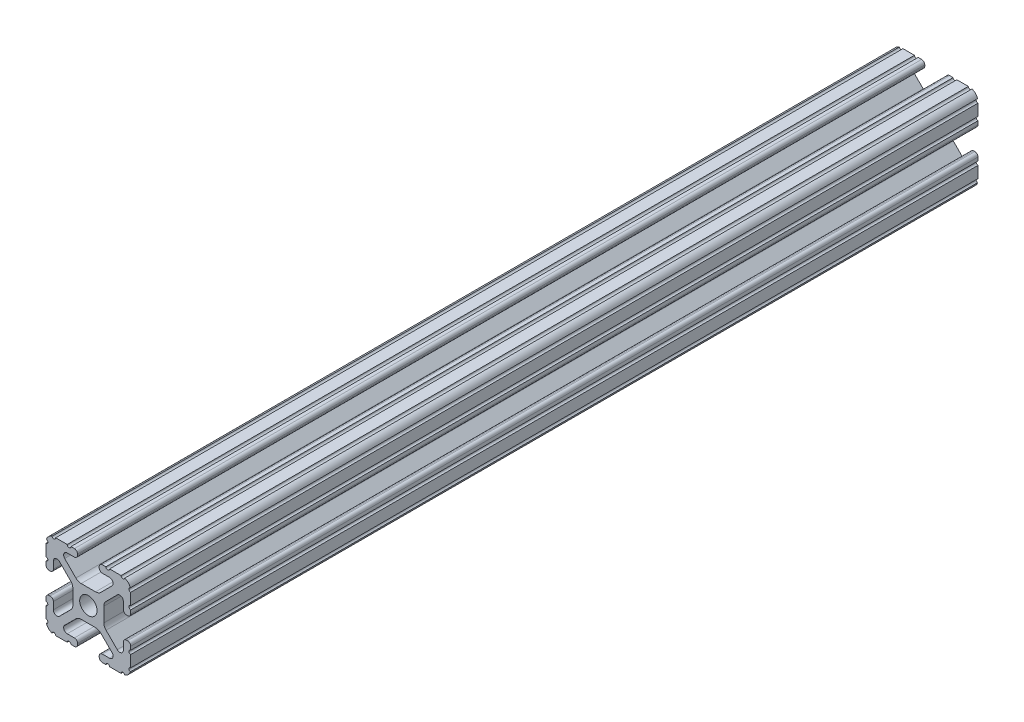
SolidWorks part; units mm, degrees
ref_plane "Front Plane" through (0, 0, 0) normal (0, 0, 1) x (1, 0, 0)
ref_plane "Top Plane" through (0, 0, 0) normal (0, 1, 0) x (1, 0, 0)
ref_plane "Right Plane" through (0, 0, 0) normal (1, 0, 0) x (0, 0, -1)
sketch "Sketch2" plane through (0, 0, 0) normal (0, 0, 1) x (1, 0, 0)
  line L0 (0, 12.7) -> (0, -12.7) construction
  line L1 (-12.7, 0) -> (12.7, 0) construction
  line L2 (3.2512, -12.7) -> (12.7, -12.7)
  line L3 (12.7, -12.7) -> (12.7, -3.2512)
  line L4 (3.2512, -12.7) -> (3.2512, -10.4902)
  line L5 (3.2512, -10.4902) -> (8.9276, -10.4902)
  line L6 (8.9276, -10.4902) -> (3.0856, -4.6482)
  line L7 (0, 0) -> (12.7, -12.7) construction
  line L8 (12.7, -3.2512) -> (10.4902, -3.2512)
  line L9 (10.4902, -3.2512) -> (10.4902, -8.9276)
  line L10 (10.4902, -8.9276) -> (4.6482, -3.0856)
  circle A0 centre (0, 0) radius 2.6035
  arc A1 (6.3485, -10.4902) -> (7.1039, -8.6665) centre (6.3485, -9.4219) ccw construction
  point P8 (0, -4.6482)
  dimension "Center Hole Diameter" = 5.207
  dimension "Rail Height" = 25.4
  dimension "Rail Width" = 25.4
  dimension "T-Slot Width" = 6.5024
  dimension "Slot Inner Width" = 14.8336
  dimension "Thickness" = 2.2098
  dimension "Slot Depth" = 5.842
  dimension "D1" = 2.2098
sketch "Sketch3" plane through (0, 0, 0) normal (1, 0, 0) x (0, 0, -1)
  line L0 (-152.4, -12.7) -> (152.4, -12.7) construction
  line L1 (-127, 0) -> (127, 0) construction
  dimension "Length" = 304.8
  dimension "D1" = 25.4
sketch "Sketch4" plane through (0, 0, 0) normal (0, 0, 1) x (1, 0, 0)
  line L0 (4.1904, -12.7) -> (10.1173, -12.7)
  line L1 (3.2512, -12.7) -> (12.7, -12.7) construction
  line L2 (3.2512, -12.7) -> (3.2512, -10.4902) construction
  line L3 (3.2512, -10.4902) -> (8.9276, -10.4902) construction
  line L4 (3.2512, -11.4294) -> (3.2512, -11.7608)
  line L5 (4.1904, -10.4902) -> (6.3485, -10.4902)
  line L6 (0, -4.6482) -> (2.164, -4.6482)
  line L7 (8.9276, -10.4902) -> (3.0856, -4.6482) construction
  line L8 (3.7373, -5.2999) -> (7.1039, -8.6665)
  line L9 (12.7, -12.7) -> (12.7, -3.2512) construction
  line L10 (10.4902, -8.9276) -> (4.6482, -3.0856) construction
  line L11 (10.4902, -3.2512) -> (10.4902, -8.9276) construction
  line L12 (10.4902, -6.3485) -> (10.4902, -4.1904)
  line L13 (12.7, -3.2512) -> (10.4902, -3.2512) construction
  line L14 (11.4294, -3.2512) -> (11.7608, -3.2512)
  line L15 (12.7, -4.1904) -> (12.7, -10.1173)
  line L16 (8.6665, -7.1039) -> (5.2999, -3.7373)
  line L17 (4.6482, 0) -> (4.6482, -2.164)
  line L18 (-12.7, 0) -> (12.7, 0) construction
  line L19 (0, -4.6482) -> (0, -2.6035)
  line L20 (0, 12.7) -> (0, -12.7) construction
  line L21 (4.6482, 0) -> (2.6035, 0)
  arc A0 (3.2512, -11.7608) -> (4.1904, -12.7) centre (4.1904, -11.7608) ccw
  arc A2 (3.2512, -11.4294) -> (4.1904, -10.4902) centre (4.1904, -11.4294) cw
  arc A3 (6.3485, -10.4902) -> (7.1039, -8.6665) centre (6.3485, -9.4219) ccw
  arc A4 (2.164, -4.6482) -> (3.7373, -5.2999) centre (2.164, -6.8732) cw
  arc A5 (10.1173, -12.7) -> (12.7, -10.1173) centre (10.1173, -10.1173) ccw
  arc A6 (8.6665, -7.1039) -> (10.4902, -6.3485) centre (9.4219, -6.3485) ccw
  arc A7 (10.4902, -4.1904) -> (11.4294, -3.2512) centre (11.4294, -4.1904) cw
  arc A8 (11.7608, -3.2512) -> (12.7, -4.1904) centre (11.7608, -4.1904) cw
  arc A9 (5.2999, -3.7373) -> (4.6482, -2.164) centre (6.8732, -2.164) cw
  circle A10 centre (0, 0) radius 2.6035 construction
  arc A11 (0, -2.6035) -> (2.6035, 0) centre (0, 0) ccw
  dimension "D1" = 2.5827
  dimension "D2" = 2.225
  dimension "D3" = 0.9392
extrude "Boss-Extrude1" add sketch "Sketch4" along normal mid plane 304.8
sketch "Sketch5" plane through (0, 0, 0) normal (0, 0, 1) x (1, 0, 0)
  line L0 (3.2512, -12.7) -> (12.7, -12.7) construction
  line L1 (4.1904, -10.4902) -> (6.3485, -10.4902) construction
  line L3 (0, 0) -> (12.7, -12.7) construction
  line L4 (6.3485, -10.4902) -> (6.3485, -12.7) construction
  line L5 (8.9276, -10.4902) -> (3.0856, -4.6482) construction
  circle A0 centre (10.3562, -12.7) radius 0.5524
  circle A1 centre (5.796, -12.7) radius 0.5524
  circle A2 centre (12.7, -10.3562) radius 0.5524
  circle A3 centre (12.7, -5.796) radius 0.5524
  point P10 (5.2694, -10.4902)
  point P12 (9.4219, -6.3485)
  dimension "D1" = 1.1049
extrude "Cut-Extrude1" cut sketch "Sketch5" against normal through all both and the other way through all
mirror "Mirror1" about plane through (0, 0, 0) normal (1, 0, 0) of bodies 137 134
mirror "Mirror2" about plane through (0, 0, 0) normal (0, 1, 0) of bodies 135
sketch "Sketch6" plane through (-4.6482, 0, 0) normal (-1, 0, 0) x (0, 0, 1)
  line L0 (-152.4, -2.164) -> (-152.4, 2.164) construction
  line L1 (-152.4, 0) -> (-95.3043, 0) construction
  circle A0 centre (-139.7, 0) radius 2.6035
  circle A1 centre (-63.5, 0) radius 2.6035
  dimension "D1" = 5.207
  dimension "D3" = 5.207
  dimension "D2" = 12.7
  dimension "D4" = 76.2
extrude "Cut-Extrude2" cut sketch "Sketch6" against normal blind 38.1
sketch "Sketch7" plane through (-12.7, 0, 0) normal (-1, 0, 0) x (0, 0, 1)
  line L5 (152.4, -17.7226) -> (101.6, -17.7226)
  line L6 (152.4, -17.7226) -> (152.4, 33.134)
  line L7 (152.4, 33.134) -> (101.6, 33.134)
  line L8 (101.6, -17.7226) -> (101.6, 33.134)
  dimension "D1" = 50.8
  dimension "D2" = 50.8566
extrude "Cut-Extrude3" cut sketch "Sketch7" against normal blind 61.468 and the other way blind 61.468
equation "\"D1@Boss-Extrude1\"=\"Length@Sketch3\""
equation "\"D1@Sketch2\"=\"Thickness@Sketch2\""
equation "\"D2@Sketch4\"=\"Slot Inner Width@Sketch2\"*0.15"
equation "\"D1@Sketch4\"=\"D3@Sketch4\"*2.75"
equation "\"D3@Sketch4\"=\"Thickness@Sketch2\"*0.425"
equation "\"D1@Sketch5\"=\"Thickness@Sketch2\"*0.5"
